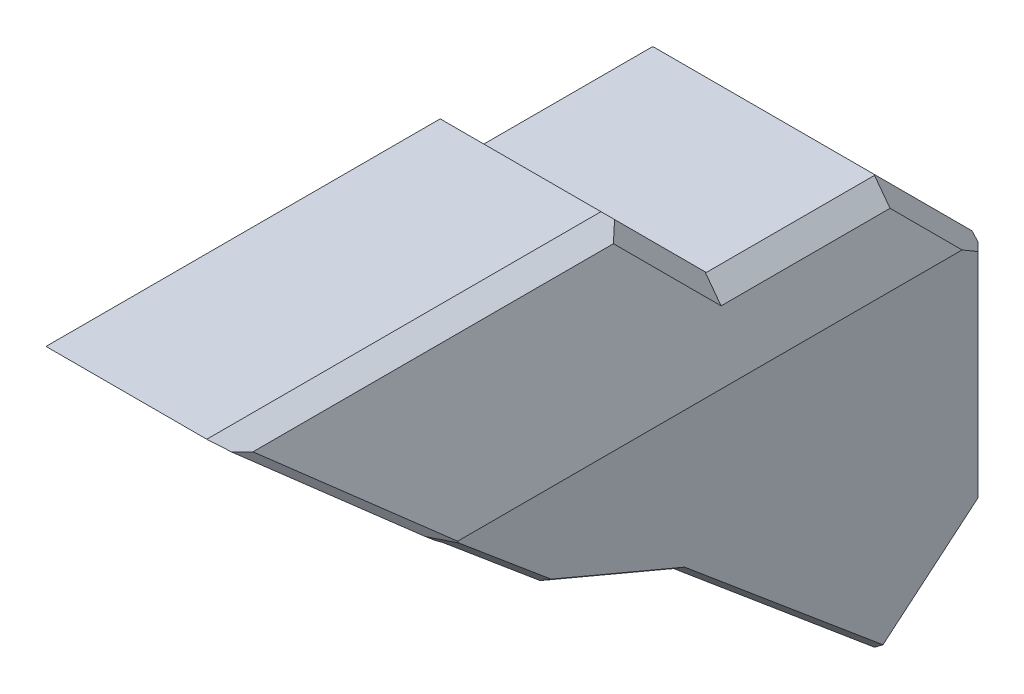
SolidWorks part; units mm, degrees
note: The reader was unsure of these and kept them because the rebuilt part matched: shared geometry of "草图5<2>".
ref_plane "前视基准面" through (0, 0, 0) normal (0, 0, 1) x (1, 0, 0)
ref_plane "上视基准面" through (0, 0, 0) normal (0, 1, 0) x (1, 0, 0)
ref_plane "右视基准面" through (0, 0, 0) normal (1, 0, 0) x (0, 0, -1)
sketch "草图2" plane through (0, 0, 0) normal (0, 0, 1) x (1, 0, 0)
  line L0 (-53, 45) -> (-34, 95)
  line L1 (50, 44.4492) -> (50, -65)
  line L2 (50, -65) -> (53, -65)
  line L3 (53, -65) -> (53, 45)
  line L4 (-34, 95) -> (-30.7907, 95)
  line L5 (-53, 45) -> (-53, -65)
  line L6 (-53, -65) -> (-50, -65)
  line L7 (-50, -65) -> (-50, 44.4492)
  line L8 (-30.7907, 95) -> (-50, 44.4492)
  line L9 (53, 45) -> (34, 95)
  line L10 (34, 95) -> (30.7907, 95)
  line L11 (30.7907, 95) -> (50, 44.4492)
  dimension "D1" = 65
  dimension "D2" = 100
  dimension "D3" = 50
  dimension "D4" = 50
  dimension "D5" = 65
  dimension "D6" = 110
  dimension "D7" = 3
  dimension "D8" = 160
  dimension "D9" = 3
  dimension "D10" = 160
  dimension "D11" = 110
  dimension "D12" = 68
  dimension "D13" = 34
  dimension "D14" = 3
  dimension "D15" = 3
extrude "凸台-拉伸1" add sketch "草图2" along normal blind 250
sketch "草图3" plane through (0, 0, 0) normal (1, 0, 0) x (0, 0, -1)
  line L0 (0, -35) -> (-35.7526, -65)
  line L1 (0, 45) -> (0, -65) construction
  line L2 (-250, -65) -> (0, -65) construction
  line L3 (-35.7526, -65) -> (-107.2578, -5)
  line L4 (-107.2578, -5) -> (-154.6597, 15)
  line L5 (-154.6597, 15) -> (-250, 95)
  line L6 (0, -35) -> (0, -65)
  line L7 (0, -65) -> (0, -69.5579)
  line L8 (0, -69.5579) -> (-250, -69.5579)
  line L9 (-250, -65) -> (-250, 95)
  line L10 (-250, 95) -> (0, 95) construction
  line L11 (-110, 95) -> (-85, 70)
  line L12 (-85, 70) -> (-25, 70)
  line L14 (-25, 70) -> (0, 45)
  line L15 (-110, 95) -> (0, 95)
  line L16 (-250, -69.5579) -> (-250, -65)
  line L17 (0, 45) -> (0, 95)
  line L18 (-250, 95) -> (0, 95) construction
  dimension "D1" = 30
  dimension "D2" = 40
  dimension "D3" = 40
  dimension "D4" = 60
  dimension "D5" = 80
  dimension "D6" = 135
  dimension "D7" = 110
  dimension "D8" = 65
  dimension "D9" = 25
  dimension "D10" = 45
extrude "切除-拉伸1" cut sketch "草图3" against normal through all both and the other way through all
sketch "草图5" plane through (0, 0, 0) normal (1, 0, 0) x (0, 0, -1)
  line L0 (-250, 95) -> (-110, 95)
  line L1 (-110, 95) -> (-85, 70)
  line L2 (-85, 70) -> (-25, 70)
  line L3 (-25, 70) -> (0, 45)
  line L4 (0, 45) -> (0, -35)
  line L5 (0, -35) -> (-4, -35)
  line L6 (-4, -35) -> (-4, 43.3431)
  line L7 (-4, 43.3431) -> (-26.6569, 66)
  line L8 (-26.6569, 66) -> (-86.6569, 66)
  line L9 (-86.6569, 66) -> (-111.6569, 91)
  line L10 (-111.6569, 91) -> (-245.233, 91)
  line L11 (-250, 95) -> (-190.4123, 45) construction
  line L12 (-245.233, 91) -> (-250, 95)
  dimension "D1" = 4
  dimension "D2" = 4
  dimension "D3" = 4
  dimension "D4" = 4
  dimension "D5" = 4
extrude "凸台-拉伸5" add sketch "草图5" along normal up to next
extrude "凸台-拉伸6" add sketch "草图5<2>" against normal up to next
sketch "草图5<2>" plane through (0, 0, 0) normal (1, 0, 0) x (0, 0, -1) same geometry as "草图5"
sketch "草图13" plane through (0, 0, 4) normal (0, 0, 1) x (1, 0, 0)
  line L0 (-5, 15) -> (35.7, 15)
  line L1 (35.7, 15) -> (35.7, -15)
  line L2 (35.7, -15) -> (-5, -15)
  line L3 (-5, -15) -> (-5, -19)
  line L4 (-5, -19) -> (38.7, -19)
  line L5 (38.7, -19) -> (38.7, 18)
  line L6 (38.7, 18) -> (-5, 18)
  line L7 (-5, 18) -> (-5, 15)
  line L8 (50, 43.3431) -> (50, -35) construction
  dimension "D1" = 15
  dimension "D2" = 15
  dimension "D3" = 14.3
  dimension "D4" = 3
  dimension "D5" = 3
  dimension "D6" = 4
  dimension "D7" = 5
  dimension "D8" = 5
extrude "凸台-拉伸13" add sketch "草图13" along normal blind 52
sketch "草图15" plane through (0, 0, 4) normal (0, 0, 1) x (1, 0, 0)
  line L0 (-5, 15) -> (35.7, 15) construction
  line L1 (30.7, 15) -> (28.7, 15)
  line L2 (30.7, 15) -> (30.7, 10)
  line L3 (30.7, 10) -> (28.7, 10)
  line L4 (28.7, 15) -> (28.7, 10)
  line L5 (35.7, -15) -> (-5, -15) construction
  line L6 (30.7, -15) -> (28.7, -15)
  line L7 (30.7, -15) -> (30.7, -10)
  line L8 (30.7, -10) -> (28.7, -10)
  line L9 (28.7, -15) -> (28.7, -10)
  line L10 (35.7, 15) -> (35.7, -15) construction
  line L11 (-12, 1) -> (-8, 1)
  line L12 (-12, 1) -> (-12, -1)
  line L13 (-12, -1) -> (-8, -1)
  line L14 (-8, 1) -> (-8, -1)
  dimension "D1" = 5
  dimension "D2" = 2
  dimension "D3" = 5
  dimension "D4" = 5
  dimension "D5" = 2
  dimension "D6" = 5
  dimension "D7" = 8
  dimension "D8" = 4
  dimension "D9" = 1
  dimension "D10" = 1
extrude "凸台-拉伸14" add sketch "草图15" along normal blind 12
sketch "草图16" plane through (0, 0, 4) normal (0, 0, 1) x (1, 0, 0)
  line L0 (-50, 43.3431) -> (-50, -35) construction
  line L1 (-19.8, 16) -> (-29.8, 16)
  line L2 (-19.8, 16) -> (-19.8, -16)
  line L3 (-19.8, -16) -> (-29.8, -16)
  line L4 (-29.8, 16) -> (-29.8, -16)
  dimension "D1" = 30.2
  dimension "D2" = 10
  dimension "D3" = 16
  dimension "D4" = 16
extrude "凸台-拉伸15" add sketch "草图16" along normal blind 12
sketch "草图17" plane through (-19.8, 0, 0) normal (1, 0, 0) x (0, 0, -1)
  line L0 (-16, -16) -> (-16, 16) construction
  circle A0 centre (-11.5, 8.5) radius 1.5
  circle A1 centre (-11.5, -8.5) radius 1.5
  dimension "D5" = 3
  dimension "D6" = 3
  dimension "D1" = 4.5
  dimension "D2" = 4.5
  dimension "D3" = 8.5
  dimension "D4" = 8.5
extrude "切除-拉伸2" cut sketch "草图17" against normal up to next
sketch "草图18" plane through (0, 0, 0) normal (0, 0, -1) x (-1, 0, 0)
  circle A0 centre (20.5, 0) radius 1.5
  circle A1 centre (14.4957, -14.4957) radius 1.5
  circle A2 centre (0, -20.5) radius 1.5
  circle A3 centre (-14.4957, -14.4957) radius 1.5
  circle A4 centre (-20.5, 0) radius 1.5
  circle A5 centre (-14.4957, 14.4957) radius 1.5
  circle A6 centre (0, 20.5) radius 1.5
  circle A7 centre (14.4957, 14.4957) radius 1.5
  circle A8 centre (0, 0) radius 4.6154
  point P19 (0, 0)
  dimension "D1" = 3
  dimension "D2" = 20.5
  dimension "D3" = 8
extrude "切除-拉伸3" cut sketch "草图18" against normal blind 10
chamfer "倒角1" distance 2 angle 60 10 edges at (43.5, 70, 220.2062) (53, 30, 172.536) (53, 5, 130.9588) (53, -35, 71.5052) (53, -50, 17.8763) (-43.5, 70, 220.2062) (-53, 30, 172.536) (-53, 5, 130.9588) (-53, -35, 71.5052) (-53, -50, 17.8763)
chamfer "倒角2" distance 4 angle 45 16 edges at (45.9054, 55.2246, 15.8815) (-45.9054, 55.2246, 15.8815) (41.8107, 66, 56.6569) (-41.8107, 66, 56.6569) (37.0607, 78.5, 99.1569) (-37.0607, 78.5, 99.1569) (32.3107, 91, 178.4449) (-32.3107, 91, 178.4449) (-48.25, 57.5, 12.5) (48.25, 57.5, 12.5) (-43.5, 70, 55) (43.5, 70, 55) (-38.75, 82.5, 97.5) (38.75, 82.5, 97.5) (-34, 95, 178.1913) (34, 95, 178.1913)
chamfer "倒角4" distance 2 angle 45 4 edges at (-50, 2.305, 4) (50, 2.1538, 4) (-53, 5.0154, 0) (53, 4.0597, 0)
